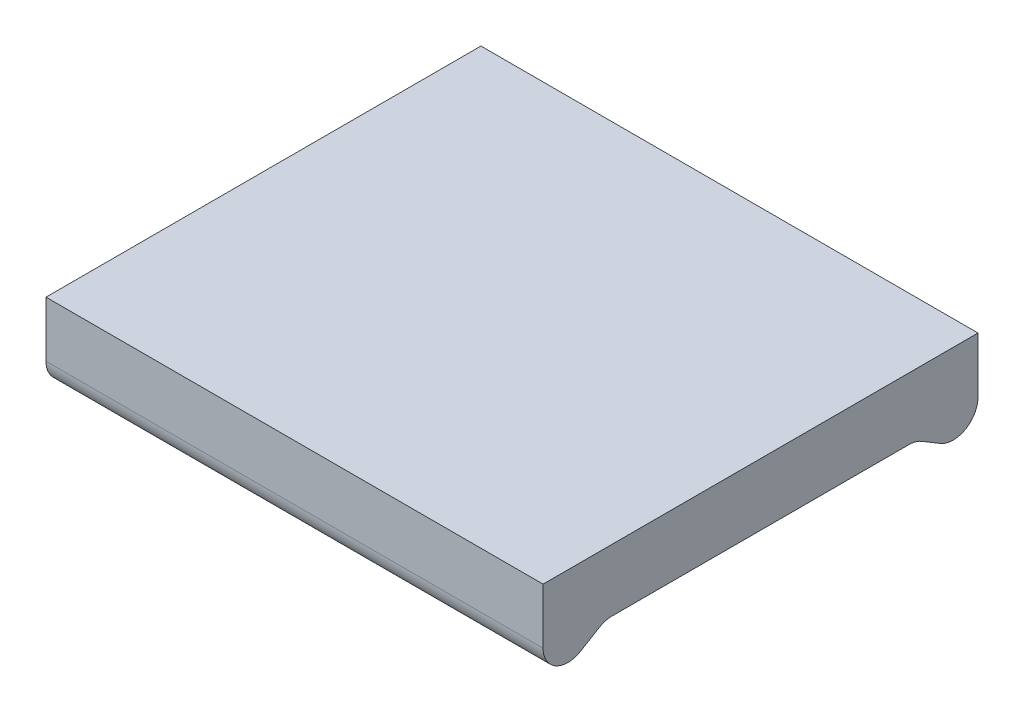
SolidWorks part; units mm, degrees
material "PEI"
ref_plane "Front Plane" through (0, 0, 0) normal (0, 0, 1) x (1, 0, 0)
ref_plane "Top Plane" through (0, 0, 0) normal (0, 1, 0) x (1, 0, 0)
ref_plane "Right Plane" through (0, 0, 0) normal (1, 0, 0) x (0, 0, -1)
sketch "Sketch1" plane through (0, 0, 0) normal (0, 1, 0) x (1, 0, 0)
  line L1 (20, -17.5) -> (-20, -17.5)
  line L2 (20, -17.5) -> (20, 17.5)
  line L3 (20, 17.5) -> (-20, 17.5)
  line L4 (-20, -17.5) -> (-20, 17.5)
  line L5 (20, -17.5) -> (-20, 17.5) construction
  line L6 (20, 17.5) -> (-20, -17.5) construction
  point P0 (0, 0)
  dimension "D1" = 35
  dimension "D2" = 40
extrude "Boss-Extrude1" add sketch "Sketch1" against normal blind 8
sketch "Sketch2" plane through (20, 0, 0) normal (1, 0, 0) x (0, 0, -1)
  line L0 (-17.5, -8) -> (-12.5, -5)
  line L1 (-12.5, -5) -> (12.5, -5)
  line L2 (0, -5) -> (0, -8)
  line L3 (17.5, -8) -> (12.5, -5)
  line L4 (17.5, 0) -> (-17.5, 0)
  line L5 (-17.5, 0) -> (-17.5, -8)
  line L6 (-17.5, -8) -> (17.5, -8)
  line L7 (17.5, -8) -> (17.5, 0)
  line L8 (17.5, 0) -> (-17.5, 0)
  line L9 (-17.5, 0) -> (-17.5, -8)
  line L10 (-17.5, -8) -> (17.5, -8)
  line L11 (17.5, -8) -> (17.5, 0)
  line M7 (-17.5, -8) -> (17.5, -8)
  dimension "D2" = 5
  dimension "D3" = 3
  dimension "D1" = 0
extrude "Cut-Extrude1" cut sketch "Sketch2" against normal through all and the other way through all contours L2 L1 L0 M7 | L3 L1 L2 M7 region at (20, -6.5833, 7.5694) region at (20, -6.5833, -7.5694)
fillet "Fillet1" radius 2 4 edges at (0, -5, 12.5) (0, -5, -12.5) (0, -8, -17.5) (0, -8, 17.5)
